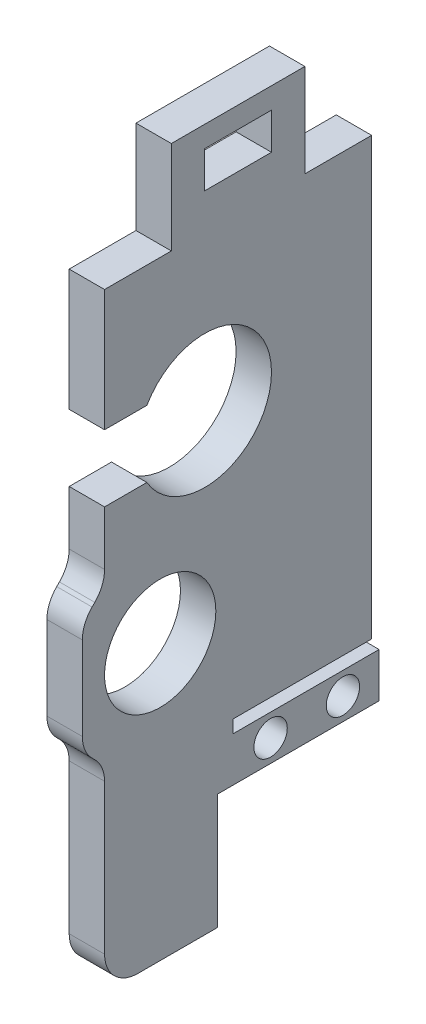
SolidWorks part; units mm, degrees
note: The reader was unsure of these and kept them because the rebuilt part matched: shared geometry of "Sketch2<4>".
ref_plane "Front Plane" through (0, 0, 0) normal (0, 0, 1) x (1, 0, 0)
ref_plane "Top Plane" through (0, 0, 0) normal (0, 1, 0) x (1, 0, 0)
ref_plane "Right Plane" through (0, 0, 0) normal (1, 0, 0) x (0, 0, -1)
sketch "Sketch2" plane through (0, 0, 0) normal (1, 0, 0) x (0, 0, -1)
  line L0 (0, 54.73) -> (24, 54.73)
  line L1 (24, 54.73) -> (24, 15.53)
  line L2 (10.17, 0) -> (0, 0)
  line L3 (-2, 19.7) -> (-2, 29.7)
  line L4 (-14.1477, -4) -> (43.3175, -4) construction
  line L14 (0, 31.7) -> (0, 37.8109)
  line L16 (0, 17.7) -> (0, 0)
  line L19 (10.17, 0) -> (10.17, 10.38)
  line L20 (10.17, 10.38) -> (24.67, 10.38)
  line L25 (-2, 29.7) -> (0, 31.7)
  line L26 (-2, 19.7) -> (0, 17.7)
  line L28 (5, 29.7) -> (-2, 29.7) construction
  line L29 (5, 19.7) -> (-2, 19.7) construction
  line L31 (11.52, 15.53) -> (11.52, 14.38)
  line L40 (24.67, 14.38) -> (24.67, 10.38)
  line L41 (24.67, 14.38) -> (11.52, 14.38)
  line L44 (3.8038, 43.8109) -> (0, 43.8109)
  line L46 (3.8038, 37.8109) -> (0, 37.8109)
  line L47 (0, 43.8109) -> (0, 54.73)
  line L48 (11.52, 15.53) -> (24, 15.53)
  circle A1 centre (5, 24.7) radius 5
  circle A2 centre (9, 40.8109) radius 8 construction
  circle A3 centre (9, 40.8109) radius 5 construction
  arc A5 (3.8038, 37.8109) -> (3.8038, 43.8109) centre (9, 40.8109) ccw
  dimension "D1" = 28.7
  dimension "D2" = 4
  dimension "D4" = 24
  dimension "D6" = 16
  dimension "D7" = 10
  dimension "D3" = 10
  dimension "D10" = 2
  dimension "D9" = 2
  dimension "D19" = 12
  dimension "D5" = 16.6
  dimension "D8" = 9
  dimension "D11" = 1.15
  dimension "D12" = 10.38
  dimension "D13" = 4
  dimension "D14" = 13.15
  dimension "D15" = 1.35
  dimension "D16" = 10.17
  dimension "D17" = 39.2
  dimension "D18" = 6
extrude "Boss-Extrude1" add sketch "Sketch2" against normal blind 3.18 contours L0 L1 L48 L31 L41 L40 L20 L19 L2 L16 L26 L3 L25 L14 L46 A5 L44 L47
extrude "Cut-Extrude2" cut sketch "Sketch2<4>" against normal blind 3.18 flip side to cut
sketch "Sketch2<4>" plane through (0, 0, 0) normal (1, 0, 0) x (0, 0, -1) same geometry as "Sketch2"
fillet "Fillet6" radius 3 5 edges at (-1.59, 17.7, 0) (-1.59, 19.7, 2) (-1.59, 29.7, 2) (-1.59, 31.7, 0) (-1.59, 0, 0)
hole_wizard "M2x0.4 Tapped Hole1" [suppressed] positions "Sketch5" profile "Sketch6" tap size "M2x0.4" standard "ANSI Metric"
sketch "Sketch5" plane through (0, 53.79, 0) normal (0, 1, 0) x (1, 0, 0)
  line L0 (-3.18, 24) -> (0, 24) construction
  line L1 (-3.18, 0) -> (0, 0) construction
  line L2 (0, 0) -> (0, 24) construction
  point P0 (-1.59, 21.5)
  point P2 (-1.59, 2.5)
  point P13 (-1.59, 21.5)
  dimension "D1" = 2.5
  dimension "D2" = 2.5
  dimension "D3" = 1.59
sketch "Sketch6" plane through (-1.59, 53.79, -21.5) normal (1, 0, 0) x (0, 0, 1)
  line L0 (0, 0) -> (0, 6)
  line L1 (0, 6) -> (0.8, 5.5193)
  line L2 (0.8, 5.5193) -> (0.8, 0)
  line L5 (0.8, 0) -> (0, 0)
  line L10 (0, 6) -> (-0.8, 5.5193) construction
  line L11 (0, -6.35) -> (0, 107.95) construction
  dimension "Tap Drill Dia." = 1.6
  dimension "Tap Drill Depth" = 6
  dimension "Drill Angle" = 118
mirror "Mirror1" about plane through (0, 40.8109, -9) normal (1, 0, 0) of bodies 102 104
delete or keep bodies "Body-Delete/Keep 1" type delete bodies bodies 102
hole_wizard "M3.5x0.6 Tapped Hole1" positions "Sketch7" profile "Sketch8" tap size "M3.5x0.6" standard "ANSI Metric" end condition up to next
sketch "Sketch7" plane through (3.18, 0, 0) normal (1, 0, 0) x (0, 0, -1)
  line L0 (24.67, 14.38) -> (11.52, 14.38) construction
  line L1 (24.67, 14.38) -> (24.67, 10.38) construction
  point P0 (21.42, 12.38)
  point P2 (14.92, 12.38)
  dimension "D1" = 2
  dimension "D2" = 3.25
  dimension "D4" = 6.5
sketch "Sketch8" plane through (3.18, 12.38, -21.42) normal (0, 1, 0) x (0, 0, -1)
  line L0 (0, 0) -> (0, 3.18)
  line L1 (0, 3.18) -> (1.5, 3.18)
  line L2 (1.5, 3.18) -> (1.5, 0)
  line L5 (1.5, 0) -> (0, 0)
  line L11 (0, -6.35) -> (0, 107.95) construction
  dimension "Thru Tap Drill Dia." = 3
  dimension "Thru Tap Drill Depth" = 3.18
cosmetic thread "Hole Thread1" parameters "D2"=3.5
cosmetic thread "Hole Thread2" parameters "D2"=3.5
sketch "Sketch9" plane through (0, 54.73, 0) normal (0, 1, 0) x (1, 0, 0)
  line L0 (0, 24) -> (3.18, 0) construction
  line L1 (3.18, 0) -> (3.18, 24) construction
  line L2 (0, 18) -> (3.18, 18)
  line L3 (0, 18) -> (0, 6)
  line L4 (0, 6) -> (3.18, 6)
  line L5 (3.18, 18) -> (3.18, 6)
  line L6 (0, 18) -> (3.18, 6) construction
  line L7 (0, 6) -> (3.18, 18) construction
  point P4 (1.59, 12)
  dimension "D1" = 12
extrude "Boss-Extrude2" add sketch "Sketch9" along normal blind 8.36 contours L3 L2 L5 L4
sketch "Sketch10" plane through (3.18, 0, 0) normal (1, 0, 0) x (0, 0, -1)
  line L0 (6, 54.73) -> (18, 54.73) construction
  line L2 (9, 61.19) -> (15, 61.19)
  line L3 (9, 61.19) -> (9, 57.91)
  line L4 (9, 57.91) -> (15, 57.91)
  line L5 (15, 61.19) -> (15, 57.91)
  line L6 (9, 61.19) -> (15, 57.91) construction
  line L7 (9, 57.91) -> (15, 61.19) construction
  point P4 (12, 59.55)
  point P12 (12, 54.73)
  dimension "D1" = 3.28
  dimension "D2" = 6
  dimension "D3" = 3.18
extrude "Cut-Extrude3" cut sketch "Sketch10" against normal through all
equation "\"RollerToBaseplate\"= 28.7mm"
equation "\"SteelShaftDia\"= 10mm"
equation "\"DribblerMotorDia\"= 16mm"
equation "\"DribblerHeight\"= 50mm"
equation "\"Width\"= 24mm"
equation "\"MaterialThickness\"= 3.18mm"
equation "\"D1@Sketch9\"=\"Width\"/2"
equation "\"D1@Boss-Extrude2\"=\"MaterialThickness\"*2 + 2mm"
equation "\"D1@Sketch10\"=\"MaterialThickness\"+0.1mm"
equation "\"D2@Sketch10\"=\"Width\"/4"
equation "\"D3@Sketch10\"=\"MaterialThickness\""
